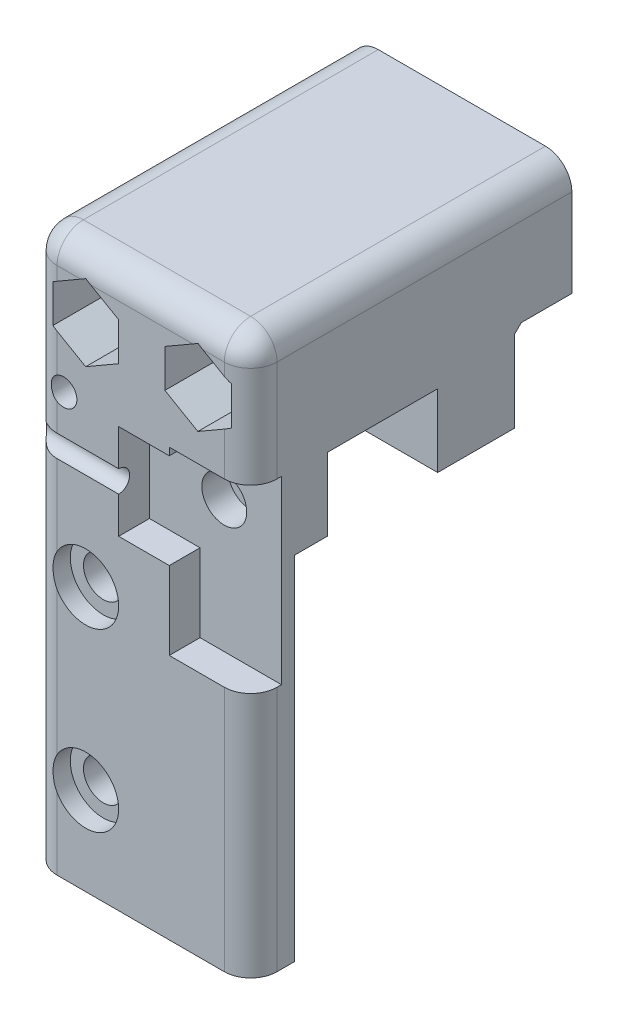
SolidWorks part; units mm, degrees
ref_plane "Front Plane" through (0, 0, 0) normal (0, 0, 1) x (1, 0, 0)
ref_plane "Top Plane" through (0, 0, 0) normal (0, 1, 0) x (1, 0, 0)
ref_plane "Right Plane" through (0, 0, 0) normal (1, 0, 0) x (0, 0, -1)
sketch "Sketch1" plane through (0, 0, 0) normal (1, 0, 0) x (0, 0, -1)
  line L1 (8.75, 0) -> (8.75, 9.25)
  line L2 (8.75, 9.25) -> (9.5, 10)
  line L3 (9.5, 10) -> (15.25, 10)
  line L4 (15.25, 10) -> (15.25, 23)
  line L5 (15.25, 23) -> (-19.25, 23)
  line L6 (-19.25, 23) -> (-19.25, -40)
  line L7 (-19.25, -40) -> (-16.25, -40)
  line L8 (-16.25, -40) -> (-16.25, 0)
  line L9 (-16.25, 0) -> (-12.5, 0)
  line L13 (0, 0) -> (3.75, 0)
  line L15 (-12.5, 0) -> (-12.25, 0) construction
  line L16 (-12.25, 0) -> (-12.25, 8) construction
  line L17 (-12.25, 8) -> (-0.25, 8) construction
  line L18 (-0.25, 8) -> (-0.25, 0) construction
  line L19 (-0.25, 0) -> (0, 0) construction
  line L20 (-12.5, 0) -> (-12.5, 8.25)
  line L21 (-12.5, 8.25) -> (0, 8.25)
  line L22 (0, 8.25) -> (0, 0)
  line L23 (8.75, 8) -> (8.75, -22) construction
  line L24 (3.75, 0) -> (8.75, 0)
  line L25 (15.25, 23) -> (15.25, 10) construction
  line L26 (15.25, 10) -> (10.75, 10) construction
  line L27 (47.75, 23) -> (15.25, 23) construction
  dimension "D3" = 12
  dimension "D4" = 8
  dimension "D1" = 20
  dimension "D5" = 225
  dimension "D6" = 0.75
  dimension "D7" = 40
  dimension "D8" = 3
extrude "Boss-Extrude1" add sketch "Sketch1" along normal blind 25
sketch "Sketch2" plane through (0, 0, 19.25) normal (0, 0, 1) x (1, 0, 0)
  line L0 (6.25, -40) -> (6.25, -30) construction
  line L2 (6.25, -30) -> (6.25, -20) construction
  line L3 (6.25, -20) -> (6.25, -10) construction
  line L4 (25, -40) -> (0, -40) construction
  line L5 (6.25, 23) -> (6.25, 16) construction
  line L6 (25, 23) -> (0, 23) construction
  line L7 (6.25, 16) -> (6.25, -10) construction
  line L8 (6.25, 16) -> (19, 16) construction
  line L9 (19, 16) -> (25, 16) construction
  line L10 (25, 23) -> (25, -40) construction
  circle A0 centre (6.25, -30) radius 2.25
  circle A1 centre (6.25, -10) radius 2 construction
  circle A2 centre (6.25, -10) radius 2.25
  circle A3 centre (6.25, 16) radius 2.25
  circle A5 centre (19, 16) radius 2.25
  dimension "D2" = 4
  dimension "D1" = 10
  dimension "D4" = 7
  dimension "D5" = 6
  dimension "D6" = 12.75
  dimension "D3" = 0.25
extrude "Cut-Extrude1" cut sketch "Sketch2" against normal up to next
sketch "Sketch3" plane through (0, 0, 19.25) normal (0, 0, 1) x (1, 0, 0)
  line L0 (10, 18.1651) -> (6.25, 20.3301)
  line L1 (9.75, 18.0207) -> (6.25, 20.0415) construction
  line L2 (6.25, 20.0415) -> (2.75, 18.0207) construction
  line L3 (2.75, 18.0207) -> (2.75, 13.9793) construction
  line L4 (0, 23) -> (0, -40)
  line L5 (0, -40) -> (25, -40)
  line L6 (25, -40) -> (25, 23)
  line L7 (25, 23) -> (0, 23)
  line L8 (0, 23) -> (0, -40)
  line L9 (0, -40) -> (25, -40)
  line L10 (25, -40) -> (25, 23)
  line L11 (25, 23) -> (0, 23)
  line L12 (2.75, 13.9793) -> (6.25, 11.9585) construction
  line L13 (6.25, 11.9585) -> (9.75, 13.9793) construction
  line L14 (9.75, 13.9793) -> (9.75, 18.0207) construction
  line L15 (6.25, 20.3301) -> (2.5, 18.1651)
  line L16 (2.5, 18.1651) -> (2.5, 13.8349)
  line L17 (2.5, 13.8349) -> (6.25, 11.6699)
  line L18 (6.25, 11.6699) -> (10, 13.8349)
  line L19 (10, 13.8349) -> (10, 18.1651)
  line L21 (19, 20.3301) -> (15.25, 18.1651)
  line L22 (15.25, 18.1651) -> (15.25, 13.8349)
  line L23 (15.25, 13.8349) -> (19, 11.6699)
  line L24 (19, 11.6699) -> (22.75, 13.8349)
  line L25 (22.75, 13.8349) -> (22.75, 18.1651)
  line L26 (22.75, 18.1651) -> (19, 20.3301)
  circle A0 centre (6.25, -10) radius 3.5 construction
  circle A1 centre (6.25, -30) radius 3.75
  circle A2 centre (6.25, -10) radius 2.25 construction
  circle A3 centre (6.25, -30) radius 2.25 construction
  circle A4 centre (6.25, -10) radius 3.75
  circle A6 centre (19, 16) radius 3.75 construction
  circle A7 centre (6.25, 16) radius 3.5 construction
  circle A8 centre (6.25, 16) radius 2.25 construction
  circle A9 centre (19, 16) radius 2.25 construction
  dimension "D3" = 7
  dimension "D4" = 7
extrude "Boss-Extrude2" add sketch "Sketch3" along normal blind 2
fillet "Fillet1" radius 3 5 edges at (0, 23, 3) (25, 23, 3) (12.5, 23, 21.25) (25, -8.5, 21.25) (0, -8.5, 21.25)
sketch "Sketch4" plane through (0, 0, 21.25) normal (0, 0, 1) x (1, 0, 0)
  line L0 (25, 8.25) -> (25, 16) construction
  line L1 (16, -11.75) -> (25, -11.75) construction
  line L2 (16, -11.75) -> (16, 8.25) construction
  line L3 (16, 8.25) -> (25, 8.25) construction
  line L5 (16, -11.75) -> (25, 8.25) construction
  line L6 (16, 8.25) -> (25, -11.75) construction
  line L7 (15.75, -12) -> (25, -12)
  line L8 (15.75, -12) -> (15.75, -3.15)
  line L9 (15.75, 8.5) -> (25, 8.5)
  line L10 (25, 8.5) -> (25, -12)
  line L11 (18.5, 8.25) -> (18.5, 3) construction
  line L12 (18.5, 3) -> (18.5, -6.5) construction
  line L13 (18.5, -6.5) -> (18.5, -11.75) construction
  line L14 (15.75, 7.65) -> (10, 7.65)
  line L15 (10, 7.65) -> (10, -3.15)
  line L16 (10, -3.15) -> (15.75, -3.15)
  line L17 (15.75, 7.65) -> (15.75, 8.5)
  line L18 (15.75, -12) -> (15.75, 8.5) construction
  line L19 (15.75, -3.15) -> (15.75, 7.65) construction
  line L20 (16, 6.65) -> (11.5, 6.65) construction
  line L21 (16, -2.15) -> (11.5, -2.15) construction
  line L22 (11.5, 6.65) -> (11.5, 7.65) construction
  line L23 (11.5, -2.15) -> (11.5, -3.15) construction
  circle A0 centre (18.5, 3) radius 2.3 construction
  circle A2 centre (18.5, 3) radius 2.55
  point P0 (20.5, -1.75)
  dimension "D3" = 0.25
  dimension "D7" = 4.6
  dimension "D1" = 9
  dimension "D2" = 20
  dimension "D4" = 9.5
  dimension "D5" = 2.5
  dimension "D8" = 1.6
  dimension "D9" = 1
  dimension "D10" = 4.5
  dimension "D11" = 8.8
  dimension "D12" = 1.5
  dimension "D6" = 0.25
extrude "Cut-Extrude2" cut sketch "Sketch4" against normal offset from surface (3.5 mm away) 1.5 up to face at (8.5, -30, 16.25)
extrude "Cut-Extrude5" cut sketch "Sketch4<3>" against normal offset from surface (6.5 mm away) 3 contours A2 region at (18.5, 3, 21.25) up to face at (16.625, 0.25, 17.75) offset beyond the face yes
sketch "Sketch4<3>" plane through (0, 0, 21.25) normal (0, 0, 1) x (1, 0, 0) same geometry as "Sketch4"
sketch "Sketch6" plane through (0, 0, 21.25) normal (0, 0, 1) x (1, 0, 0)
  line L0 (10, 2.25) -> (0, 2.25) construction
  line L1 (10, 7.65) -> (10, -3.15) construction
  line L2 (0, 0) -> (0, 8.25) construction
  line L3 (0, 2.25) -> (0, 3.5)
  line L4 (0, 3.5) -> (10, 3.5)
  line L5 (10, 3.5) -> (10, 2.25)
  line L6 (10, 2.25) -> (0, 2.25)
  dimension "D1" = 2.5
revolve "Cut-Revolve1" cut sketch "Sketch6" angle 360 about L0
sketch "Sketch5" plane through (0, 0, 17.75) normal (0, 0, 1) x (1, 0, 0)
  line L0 (6.25, 10.6699) -> (6.25, 11.6699) construction
  line L1 (1, 5.1699) -> (6.5, 5.1699)
  line L2 (1, 5.1699) -> (1, 10.6699) construction
  line L3 (1, 10.6699) -> (6.5, 10.6699)
  line L4 (6.5, 5.1699) -> (6.5, 10.6699)
  line L5 (1, 5.1699) -> (6.5, 10.6699) construction
  line L6 (1, 10.6699) -> (6.5, 5.1699) construction
  line L7 (1, 5.1699) -> (0, 5.1699)
  line L8 (0, 0) -> (0, 8) construction
  line L9 (0, 5.1699) -> (0, 10.6699)
  line L10 (0, 10.6699) -> (1, 10.6699)
  circle A0 centre (3.75, 7.9199) radius 1.25 construction
  circle A1 centre (3.75, 7.9199) radius 1.5
  point P0 (3.75, 7.9199)
  dimension "D2" = 2.5
  dimension "D3" = 1
  dimension "D4" = 5.5
  dimension "D1" = 0.25
extrude "Cut-Extrude3" cut sketch "Sketch5" against normal mid plane 2
extrude "Cut-Extrude4" cut sketch "Sketch5<2>" against normal offset from surface 1.5 and the other way up to next contours A1 up to face at (12.5, 4.125, 12.5)
sketch "Sketch5<2>" plane through (0, 0, 17.75) normal (0, 0, 1) x (1, 0, 0) same geometry as "Sketch5"
sketch "Sketch7" plane through (0, 0, 19.25) normal (0, 0, 1) x (1, 0, 0)
  line L0 (22.75, 13.8349) -> (22.75, 18.1651) construction
  line L1 (22.75, 18.1651) -> (19, 20.3301) construction
  line L2 (19, 20.3301) -> (15.25, 18.1651) construction
  line L3 (15.25, 18.1651) -> (15.25, 13.8349) construction
  line L4 (15.25, 13.8349) -> (19, 11.6699) construction
  line L5 (19, 11.6699) -> (22.75, 13.8349) construction
  line L6 (6.25, 11.6699) -> (10, 13.8349) construction
  line L7 (10, 13.8349) -> (10, 18.1651) construction
  line L8 (10, 18.1651) -> (6.25, 20.3301) construction
  line L9 (6.25, 20.3301) -> (2.5, 18.1651) construction
  line L10 (2.5, 18.1651) -> (2.5, 13.8349) construction
  line L11 (2.5, 13.8349) -> (6.25, 11.6699) construction
  line L12 (22.75, 13.8349) -> (22.75, 18.1651)
  line L13 (22.75, 18.1651) -> (19, 20.3301)
  line L14 (19, 20.3301) -> (15.25, 18.1651)
  line L15 (15.25, 18.1651) -> (15.25, 13.8349)
  line L16 (15.25, 13.8349) -> (19, 11.6699)
  line L17 (19, 11.6699) -> (22.75, 13.8349)
  line L18 (6.25, 11.6699) -> (10, 13.8349)
  line L19 (10, 13.8349) -> (10, 18.1651)
  line L20 (10, 18.1651) -> (6.25, 20.3301)
  line L21 (6.25, 20.3301) -> (2.5, 18.1651)
  line L22 (2.5, 18.1651) -> (2.5, 13.8349)
  line L23 (2.5, 13.8349) -> (6.25, 11.6699)
extrude "Cut-Extrude6" cut sketch "Sketch7" against normal blind 10
equation "\"Tolerance\" = 0.25mm"
equation "\"Pocket_Head_M5\"= 8mm"
equation "\"Pocket_Head_M4\" = 7mm"
equation "\"Pocket_Nut_M4\" = 7mm"
equation "\"Pocket_Nut_M5\"= 8mm"
equation "\"Pocket_Nut_M3\"= 5.5mm"
equation "\"Pocket_Head_M3\"= 5.5mm"
equation "\"D2@Sketch1\"=\"Tolerance\""
equation "\"D3@Sketch2\"=\"Tolerance\""
equation "\"D3@Sketch3\"=\"Pocket_Head_M4\""
equation "\"D2@Sketch3\"=\"Tolerance\""
equation "\"D4@Sketch3\"=\"Pocket_Nut_M4\""
equation "\"D5@Sketch3\"=\"Tolerance\""
equation "\"D3@Sketch4\"=\"Tolerance\""
equation "\"D1@Sketch5\"=\"Tolerance\""
equation "\"D4@Sketch5\"=\"Pocket_Nut_M3\""
equation "\"D1@Cut-Extrude3\"=( 1.5 + ( \"Tolerance\" * 2 ) )"
equation "\"D6@Sketch4\"=\"Tolerance\""
